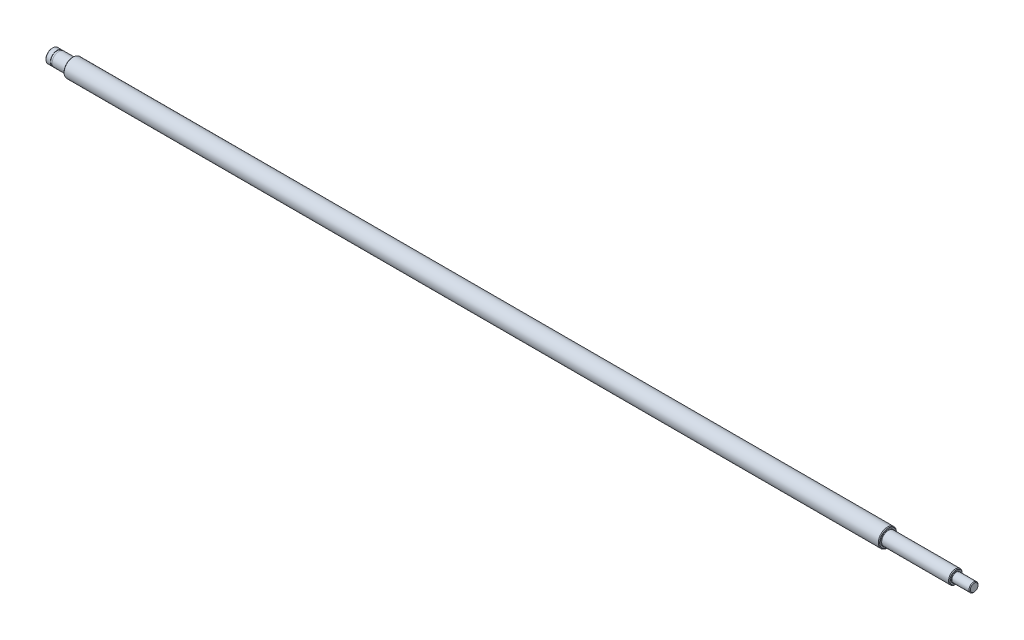
SolidWorks part; units mm, degrees
material "6061 合金"
ref_plane "前视基准面" through (0, 0, 0) normal (0, 0, 1) x (1, 0, 0)
ref_plane "上视基准面" through (0, 0, 0) normal (0, 1, 0) x (1, 0, 0)
ref_plane "右视基准面" through (0, 0, 0) normal (1, 0, 0) x (0, 0, -1)
other "Configuration Table"
ref_plane "基准面1" through (0, 0, 0) normal (0, 0, -1) x (-1, 0, 0)
sketch "草图1" plane through (0, 0, 0) normal (0, 0, -1) x (-1, 0, 0)
  line L0 (-407, 1.7) -> (-407, 0)
  line L1 (-407, 0) -> (0, 0)
  line L2 (0, 0) -> (0, 2.7)
  line L3 (0, 2.7) -> (-0.3, 3)
  line L4 (-0.3, 3) -> (-2.2, 3)
  line L5 (-2.2, 3) -> (-2.2, 2.85)
  line L6 (-2.2, 2.85) -> (-3, 2.85)
  line L7 (-3, 2.85) -> (-3, 3)
  line L8 (-3, 3) -> (-8.8, 3)
  line L9 (-9, 3.2) -> (-9, 3.7)
  line L10 (-9, 3.7) -> (-9.3, 4)
  line L11 (-9.3, 4) -> (-368.7, 4)
  line L12 (-368.7, 4) -> (-369, 3.7)
  line L13 (-369, 3.7) -> (-369, 3.2)
  line L14 (-369.2, 3) -> (-398.7, 3)
  line L15 (-398.7, 3) -> (-399, 2.7)
  line L16 (-399, 2.7) -> (-399, 2.2)
  line L17 (-399.2, 2) -> (-406.7, 2)
  line L18 (-406.7, 2) -> (-407, 1.7)
  line L19 (-407, 0) -> (0, 0) construction
  arc A0 (-8.8, 3) -> (-9, 3.2) centre (-8.8, 3.2) cw
  arc A1 (-369, 3.2) -> (-369.2, 3) centre (-369.2, 3.2) cw
  arc A2 (-399, 2.2) -> (-399.2, 2) centre (-399.2, 2.2) cw
  dimension "D1" = 5.8
  dimension "D2" = 1.9
  dimension "D3" = 0.8
  dimension "D4" = 2.7
  dimension "D5" = 0.3
  dimension "D6" = 0.5
  dimension "D7" = 29.5
  dimension "D8" = 359.4
revolve "旋转1" add sketch "草图1" angle 360 about L19 reverse direction yes
